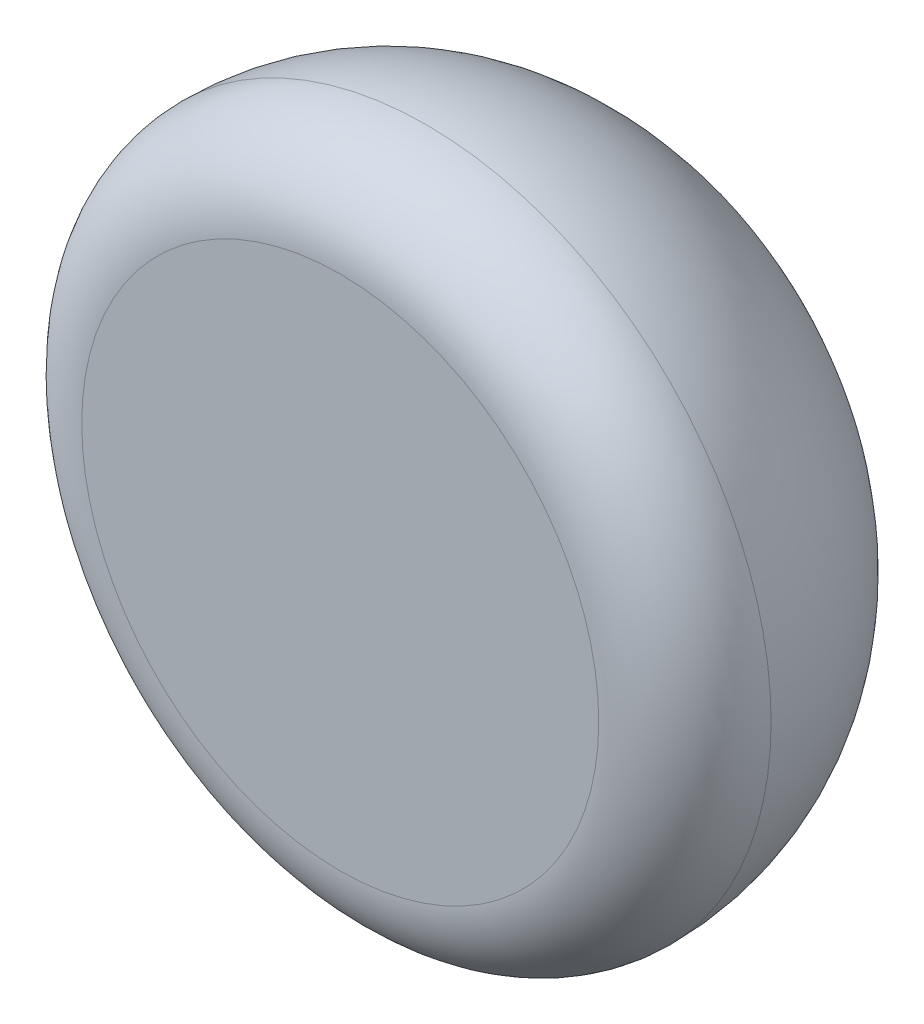
SolidWorks part; units mm, degrees
ref_plane "前视基准面" through (0, 0, 0) normal (0, 0, 1) x (1, 0, 0)
ref_plane "上视基准面" through (0, 0, 0) normal (0, 1, 0) x (1, 0, 0)
ref_plane "右视基准面" through (0, 0, 0) normal (1, 0, 0) x (0, 0, -1)
sketch "草图4" plane through (0, 0, 15.1566) normal (0, 0, 1) x (1, 0, 0)
  line L8 (63.3581, 9.5162) -> (63.3581, 11.0327)
  line L9 (62.8464, 9.0045) -> (63.3581, 9.5162)
  line L10 (61.3298, 9.0045) -> (62.8464, 9.0045)
  line L11 (60.8181, 9.5162) -> (61.3298, 9.0045)
  line L12 (60.8181, 11.0327) -> (60.8181, 9.5162)
  line L13 (61.3298, 11.5445) -> (60.8181, 11.0327)
  line L14 (62.8464, 11.5445) -> (61.3298, 11.5445)
  line L15 (63.3581, 11.0327) -> (62.8464, 11.5445)
  line L16 (63.3581, 9.5162) -> (63.3581, 11.0327)
  line L17 (62.8464, 9.0045) -> (63.3581, 9.5162)
  line L18 (61.3298, 9.0045) -> (62.8464, 9.0045)
  line L19 (60.8181, 9.5162) -> (61.3298, 9.0045)
  line L20 (60.8181, 11.0327) -> (60.8181, 9.5162)
  line L21 (61.3298, 11.5445) -> (60.8181, 11.0327)
  line L22 (62.8464, 11.5445) -> (61.3298, 11.5445)
  line L23 (63.3581, 11.0327) -> (62.8464, 11.5445)
  circle A0 centre (62.0881, 10.2745) radius 1.9043
  circle A1 centre (62.0881, 10.2745) radius 8
  circle A2 centre (62.0881, 10.2745) radius 5.23
  line M11 (63.3581, 11.0327) -> (63.3581, 9.5162)
  line M12 (63.3581, 9.5162) -> (62.8464, 9.0045)
  line M13 (62.8464, 9.0045) -> (61.3298, 9.0045)
  line M14 (61.3298, 9.0045) -> (60.8181, 9.5162)
  line M15 (60.8181, 9.5162) -> (60.8181, 11.0327)
  line M16 (60.8181, 11.0327) -> (61.3298, 11.5445)
  line M17 (61.3298, 11.5445) -> (62.8464, 11.5445)
  line M18 (62.8464, 11.5445) -> (63.3581, 11.0327)
  circle M19 centre (62.0881, 10.2745) radius 1.8843
  dimension "D2" = 16
  dimension "D1" = 0
extrude "凸台-拉伸3" add sketch "草图4" along normal blind 4 contours M19 M18 M11 M12 M13 M14 M15 M16 M17 | A1 A2 | A2 A0 region at (54.3144, 10.2745, 15.1566) region at (57.006, 10.2745, 15.1566) region at (60.2571, 10.2745, 15.1566)
extrude "凸台-拉伸4" add sketch "草图4<3>" against normal blind 1 contours A1 | A0
sketch "草图4<3>" plane through (0, 0, 15.1566) normal (0, 0, 1) x (1, 0, 0) same geometry as "草图4"
sketch "草图5" plane through (0, 0, 19.1566) normal (0, 0, 1) x (1, 0, 0)
  circle A1 centre (62.0881, 10.2745) radius 8
  circle A2 centre (62.0881, 10.2745) radius 8
  dimension "D1" = 0
extrude "凸台-拉伸5" add sketch "草图5" along normal blind 3 contours A2
fillet "圆角3" radius 2 1 edges at (70.0881, 10.2745, 22.1566)
fillet "圆角4" radius 6 1 edges at (70.0881, 10.2745, 14.1566)
